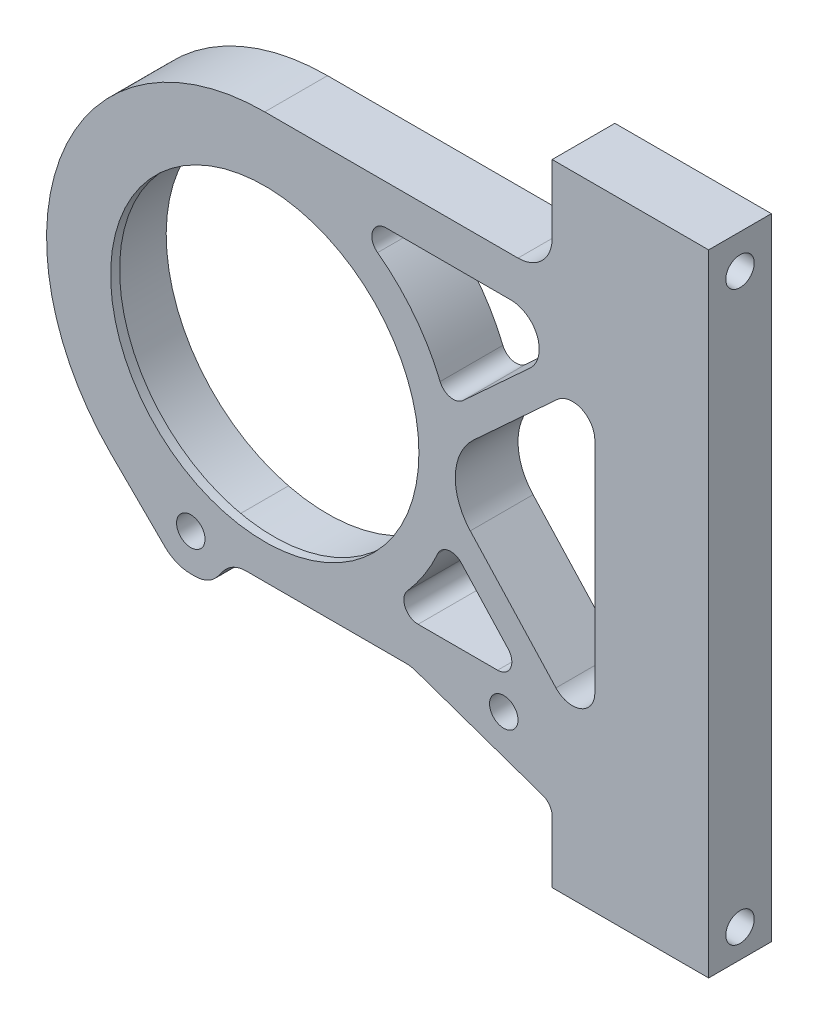
SolidWorks part; units mm, degrees
material "7075-T6 (SN)"
ref_plane "Front Plane" through (0, 0, 0) normal (0, 0, 1) x (1, 0, 0)
ref_plane "Top Plane" through (0, 0, 0) normal (0, 1, 0) x (1, 0, 0)
ref_plane "Right Plane" through (0, 0, 0) normal (1, 0, 0) x (0, 0, -1)
sketch "Sketch1" plane through (-1819.5915, 1585.914, -2825.1113) normal (0, 0, 1) x (1, 0, 0)
  line L0 (2.6847, 17.2464) -> (66.8197, 17.2464)
  line L1 (66.8197, -100.6211) -> (76.3447, -100.6211)
  line L3 (76.3447, 2.0064) -> (76.3447, -71.0301) construction
  line L4 (76.3447, 40.1064) -> (76.3447, 2.0064)
  line L5 (76.3447, -1574.5424) -> (76.3447, -1597.2856) construction
  line L6 (66.8197, 17.2464) -> (66.8197, 40.1064)
  line L7 (66.8197, 40.1064) -> (76.3447, 40.1064)
  line L8 (66.8197, -80.3011) -> (66.8197, -100.6211)
  line L12 (76.3447, -71.0301) -> (76.3447, -100.6211)
  line L13 (76.3447, 2.0064) -> (39.9547, -31.4536)
  line L14 (39.9547, -31.4536) -> (76.3447, -71.0301)
  line L15 (-19.6392, -77.9065) -> (-31.6142, -66.0263)
  line L16 (-13.8253, -80.3011) -> (66.8197, -80.3011)
  line L17 (39.9547, -31.4536) -> (38.6847, -31.4536) construction
  line L18 (38.6847, -31.4536) -> (2.6847, -31.4536) construction
  line L19 (76.3447, -72.0461) -> (56.0247, -72.0461) construction
  line L20 (56.0247, -72.0461) -> (-13.8253, -72.0461) construction
  circle A0 centre (2.6847, -31.4536) radius 36
  circle A1 centre (2.6847, -31.4536) radius 36 construction
  circle A2 centre (2.6847, -31.4536) radius 36
  arc A3 (2.6847, 17.2464) -> (-31.6142, -66.0263) centre (2.6847, -31.4536) ccw
  circle A4 centre (2.6847, -31.4536) radius 48.7 construction
  circle A6 centre (56.0247, -72.0461) radius 3.175
  circle A8 centre (-13.8253, -72.0461) radius 3.175
  circle A9 centre (89.0447, -151.2864) radius 12.7 construction
  arc A14 (-19.6392, -77.9065) -> (-13.8253, -80.3011) centre (-13.8253, -72.0461) ccw
  circle A15 centre (-13.8253, -72.0461) radius 8.255 construction
  dimension "D1" = 72
  dimension "D5" = 25.4
  dimension "D17" = 6.35
  dimension "D3" = 9.525
  dimension "D4" = 20.32
  dimension "D7" = 29.591
  dimension "D8" = 1.27
  dimension "D9" = 90
  dimension "D10" = 38.1
  dimension "D11" = 22.86
  dimension "D12" = 9.525
  dimension "D14" = 20.32
  dimension "D15" = 69.85
  dimension "D2" = 12.7
  dimension "D6" = 5.08
extrude "Boss-Extrude1" add sketch "Sketch1" along normal blind 8 and the other way blind 6
ref_plane "Plane1" through (-1752.7718, 1603.1604, -2817.1113) normal (0, 0, 1) x (1, 0, 0)
sketch "Sketch3" plane through (0, 0, -2817.1113) normal (0, 0, 1) x (1, 0, 0)
  circle A13 centre (-1816.9068, 1554.4604) radius 36 construction
  circle A14 centre (-1816.9068, 1554.4604) radius 36
  circle A15 centre (-1816.9068, 1554.4604) radius 34.4
  dimension "D1" = 68.8
extrude "Boss-Extrude2" add sketch "Sketch3" against normal blind 2
sketch "Sketch4" plane through (-1752.7718, 0, 0) normal (-1, 0, 0) x (0, 0, 1)
  line L0 (-2824.1113, 1626.0204) -> (-2824.1113, 1603.1604) construction
  line L1 (-2831.1113, 1626.0204) -> (-2817.1113, 1626.0204) construction
  line L2 (-2831.1113, 1603.1604) -> (-2817.1113, 1603.1604) construction
  line L3 (-2824.1113, 1485.2928) -> (-2824.1113, 1505.6128) construction
  line L4 (-2831.1113, 1485.2928) -> (-2817.1113, 1485.2928) construction
  line L5 (-2831.1113, 1505.6128) -> (-2817.1113, 1505.6128) construction
  circle A0 centre (-2824.1113, 1618.4004) radius 3.175
  circle A1 centre (-2824.1113, 1491.6428) radius 3.175
  dimension "D1" = 6.35
  dimension "D2" = 7.62
  dimension "D3" = 6.35
extrude "Cut-Extrude1" cut sketch "Sketch4" against normal through all
ref_plane "Plane2" through (-1816.9068, 0, 0) normal (-1, 0, 0) x (0, 0, 1)
ref_plane "Plane3" through (0, 1619.6704, 0) normal (0, 1, 0) x (1, 0, 0)
ref_plane "Plane4" through (0, 1491.6428, 0) normal (0, -1, 0) x (-1, 0, 0)
ref_point "Point3"
ref_plane "Plane5" through (0, 1513.8678, 0) normal (0, -1, 0) x (-1, 0, 0)
fillet "Fillet11" radius 12.7 1 edges at (-1779.6368, 1554.4604, -2824.1113)
sketch "Sketch6" plane through (0, 0, -2831.1113) normal (0, 0, -1) x (-1, 0, 0)
  line L0 (1743.2468, 1514.8838) -> (1771.0407, 1545.1117) construction
  line L1 (1770.288, 1563.0564) -> (1743.2468, 1587.9204) construction
  line L2 (1752.7718, 1603.1604) -> (1816.9068, 1603.1604) construction
  line L3 (1772.6838, 1569.4798) -> (1757.7121, 1583.2461)
  line L4 (1774.586, 1567.7308) -> (1747.5448, 1592.5948) construction
  line L5 (1782.6934, 1521.2338) -> (1764.9443, 1521.2338)
  line L6 (1743.2468, 1485.2928) -> (1743.2468, 1514.8838) construction
  line L7 (1824.1863, 1512.3438) -> (1784.2812, 1512.3438)
  line L12 (1743.2468, 1514.8838) -> (1771.0407, 1545.1117) construction
  line L13 (1770.288, 1563.0564) -> (1743.2468, 1587.9204) construction
  line L14 (1752.7718, 1603.1604) -> (1816.9068, 1603.1604) construction
  line L15 (1762.0101, 1594.2704) -> (1789.8419, 1594.2704)
  line L17 (1762.6071, 1526.5578) -> (1773.0615, 1537.9278)
  line L18 (1752.7718, 1594.2704) -> (1816.9068, 1594.2704) construction
  line L19 (1747.9211, 1510.5858) -> (1775.7151, 1540.8137) construction
  line L22 (1824.1863, 1512.3438) -> (1829.3409, 1505.6128)
  line L23 (1833.4168, 1505.6128) -> (1752.7718, 1505.6128) construction
  line L24 (1764.9638, 1505.6128) -> (1784.2812, 1512.3438)
  line L25 (1833.4168, 1505.6128) -> (1752.7718, 1505.6128) construction
  line L26 (1764.9638, 1505.6128) -> (1752.7718, 1505.6128)
  line L27 (1752.7718, 1505.6128) -> (1752.7718, 1485.2928)
  line L28 (1752.7718, 1485.2928) -> (1829.3409, 1505.6128)
  arc A2 (1791.7334, 1588.5453) -> (1777.7689, 1570.6087) centre (1817.018, 1554.4558) ccw
  arc A4 (1778.2954, 1537.0787) -> (1785.0824, 1526.5001) centre (1817.018, 1554.4558) ccw
  arc A5 (1785.0824, 1526.5001) -> (1782.6934, 1521.2338) centre (1782.6934, 1524.4088) cw
  arc A6 (1773.0615, 1537.9278) -> (1778.2954, 1537.0787) centre (1775.3987, 1535.7788) cw
  arc A7 (1762.6071, 1526.5578) -> (1764.9443, 1521.2338) centre (1764.9443, 1524.4088) ccw
  arc A8 (1762.0101, 1594.2704) -> (1757.7121, 1583.2461) centre (1762.0101, 1587.9204) ccw
  arc A9 (1772.6838, 1569.4798) -> (1777.7689, 1570.6087) centre (1774.8328, 1571.817) ccw
  arc A10 (1791.7334, 1588.5453) -> (1789.8419, 1594.2704) centre (1789.8419, 1591.0954) ccw
  point P18 (1776.5354, 1541.7058)
  dimension "D5" = 3.175
  dimension "D11" = 6.35
  dimension "D6" = 4.0759
  dimension "D8" = 6.35
  dimension "D9" = 8.89
  dimension "D10" = 12.192
  dimension "D1" = 8.89
  dimension "D3" = 6.35
  dimension "D4" = 6.35
extrude "Cut-Extrude2" cut sketch "Sketch6" against normal blind 22.352
sketch "Sketch7" plane through (-1752.7718, 0, 0) normal (-1, 0, 0) x (0, 0, 1)
  circle A0 centre (-2824.1113, 1618.4004) radius 6.35
  circle A1 centre (-2824.1113, 1491.6428) radius 6.35
  dimension "D1" = 12.7
split line "Split Line5"
ref_plane "Plane7" through (-1743.2468, 0, 0) normal (1, 0, 0) x (0, 0, -1)
fillet "Fillet13" radius 7.62 1 edges at (-1752.7718, 1603.1604, -2824.1113)
sketch "Sketch9" plane through (0, 0, -2817.1113) normal (0, 0, 1) x (1, 0, 0)
  line L0 (-1764.9638, 1505.6128) -> (-1752.7718, 1505.6128)
  line L1 (-1752.7718, 1505.6128) -> (-1752.7718, 1501.3647)
  line L2 (-1752.7718, 1505.6128) -> (-1752.7718, 1485.2928) construction
  line L3 (-1752.7718, 1501.3647) -> (-1764.9638, 1505.6128)
  line L6 (-1764.9638, 1505.6128) -> (-1784.2812, 1512.3438) construction
extrude "Boss-Extrude5" add sketch "Sketch9" against normal up to surface (14 mm away) up to face at (-1830.2418, 1513.8678, -2831.1113)
fillet "Fillet16" radius 6.35 3 edges at (-1829.3409, 1505.6128, -2824.1113) (-1824.1863, 1512.3438, -2824.1113) (-1784.2812, 1512.3438, -2824.1113)
ref_plane "Plane10" through (-448.0762, 1806.5349, 0) normal (0.2407, -0.9706, 0) x (0, 0, 1)
fillet "Fillet17" radius 3.175 1 edges at (-1752.7718, 1501.3647, -2824.1113)
ref_axis "Axis1" through (-1816.9068, 1554.4604, -2951.8557) along (0, 0, 1)
ref_plane "Plane11" through (-2075.4576, 517.4697, 0) normal (-0.9703, 0.2419, 0) x (0, 0, 1)
split line "Split Line6"
sketch "Sketch10" plane through (-1743.2468, 0, 0) normal (1, 0, 0) x (0, 0, -1)
  line L1 (2817.1113, 1626.0204) -> (2831.1113, 1626.0204)
  line L2 (2817.1113, 1626.0204) -> (2817.1113, 1587.9204)
  line L3 (2817.1113, 1587.9204) -> (2831.1113, 1587.9204)
  line L4 (2831.1113, 1626.0204) -> (2831.1113, 1587.9204)
  line L5 (2817.1113, 1514.8838) -> (2831.1113, 1514.8838)
  line L6 (2817.1113, 1514.8838) -> (2817.1113, 1485.2928)
  line L7 (2817.1113, 1485.2928) -> (2831.1113, 1485.2928)
  line L8 (2831.1113, 1514.8838) -> (2831.1113, 1485.2928)
  circle A0 centre (2824.1113, 1618.4004) radius 3.175
  circle A1 centre (2824.1113, 1491.6428) radius 3.175
  dimension "D1" = 6.35
  dimension "D2" = 6.35
extrude "Boss-Extrude6" add sketch "Sketch10" along normal blind 25.4
sketch "Sketch11" plane through (0, 1514.8838, 0) normal (0, 1, 0) x (1, 0, 0)
  line L1 (-1717.8468, 2817.1113) -> (-1743.2468, 2817.1113)
  line L2 (-1717.8468, 2817.1113) -> (-1717.8468, 2831.1113)
  line L3 (-1717.8468, 2831.1113) -> (-1743.2468, 2831.1113)
  line L4 (-1743.2468, 2817.1113) -> (-1743.2468, 2831.1113)
extrude "Boss-Extrude7" add sketch "Sketch11" along normal up to next
fillet "Fillet18" radius 5 2 edges at (-1743.2468, 1587.9204, -2824.1113) (-1743.2468, 1514.8838, -2824.1113)
